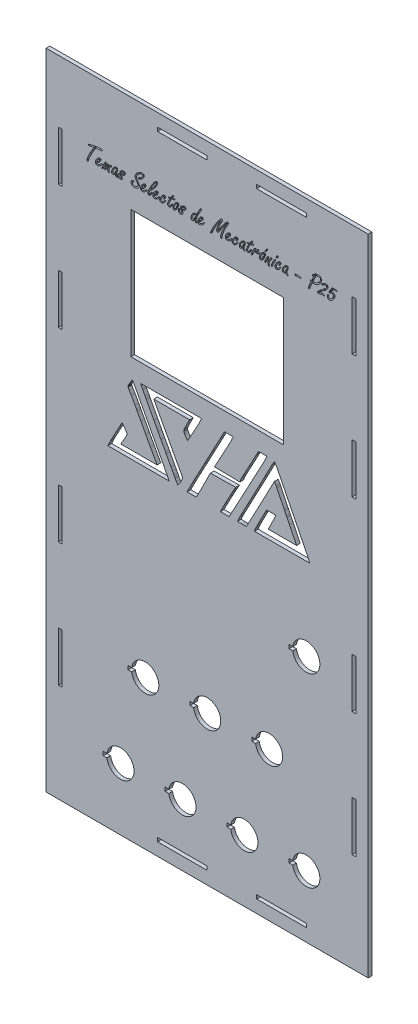
SolidWorks part; units mm, degrees
ref_plane "Alzado" through (0, 0, 0) normal (0, 0, 1) x (1, 0, 0)
ref_plane "Planta" through (0, 0, 0) normal (0, 1, 0) x (1, 0, 0)
ref_plane "Vista lateral" through (0, 0, 0) normal (1, 0, 0) x (0, 0, -1)
sketch "Croquis1" plane through (0, 0, 0) normal (0, 0, 1) x (1, 0, 0)
  line L1 (-130, 260) -> (130, 260)
  line L2 (-130, 260) -> (-130, -260)
  line L3 (-130, -260) -> (130, -260)
  line L4 (130, 260) -> (130, -260)
  line L5 (-130, 260) -> (130, -260) construction
  line L6 (-130, -260) -> (130, 260) construction
  point P0 (0, 0)
  dimension "D1" = 260
  dimension "D2" = 520
extrude "Saliente-Extruir1" add sketch "Croquis1" along normal blind 3
sketch "Croquis2" plane through (0, 0, 3) normal (0, 0, 1) x (1, 0, 0)
  line L4 (-117, -40.25) -> (-120, -40.25)
  line L5 (-117, -80.25) -> (-117, -40.25)
  line L6 (-120, -80.25) -> (-117, -80.25)
  line L7 (-120, -40.25) -> (-120, -80.25)
  line L8 (-117, -40.25) -> (-120, -40.25)
  line L9 (-117, -80.25) -> (-117, -40.25)
  line L10 (-120, -80.25) -> (-117, -80.25)
  line L11 (-120, -40.25) -> (-120, -80.25)
  line L12 (-117, 109.75) -> (-120, 109.75)
  line L13 (-117, 69.75) -> (-117, 109.75)
  line L14 (-120, 69.75) -> (-117, 69.75)
  line L15 (-120, 109.75) -> (-120, 69.75)
  line L16 (-117, 109.75) -> (-120, 109.75)
  line L17 (-117, 69.75) -> (-117, 109.75)
  line L18 (-120, 69.75) -> (-117, 69.75)
  line L19 (-120, 109.75) -> (-120, 69.75)
  line L20 (-117, 209.75) -> (-120, 209.75)
  line L21 (-117, 169.75) -> (-117, 209.75)
  line L22 (-120, 169.75) -> (-117, 169.75)
  line L23 (-120, 209.75) -> (-120, 169.75)
  line L24 (-117, 209.75) -> (-120, 209.75)
  line L25 (-117, 169.75) -> (-117, 209.75)
  line L26 (-120, 169.75) -> (-117, 169.75)
  line L27 (-120, 209.75) -> (-120, 169.75)
  line L28 (0, 249.75) -> (-40, 249.75)
  line L29 (0, 246.75) -> (0, 249.75)
  line L30 (-40, 246.75) -> (0, 246.75)
  line L31 (-40, 249.75) -> (-40, 246.75)
  line L32 (0, 249.75) -> (-40, 249.75)
  line L33 (0, 246.75) -> (0, 249.75)
  line L34 (-40, 246.75) -> (0, 246.75)
  line L35 (-40, 249.75) -> (-40, 246.75)
  line L36 (-117, -140.25) -> (-120, -140.25)
  line L37 (-117, -180.25) -> (-117, -140.25)
  line L38 (-120, -180.25) -> (-117, -180.25)
  line L39 (-120, -140.25) -> (-120, -180.25)
  line L40 (-117, -140.25) -> (-120, -140.25)
  line L41 (-117, -180.25) -> (-117, -140.25)
  line L42 (-120, -180.25) -> (-117, -180.25)
  line L43 (-120, -140.25) -> (-120, -180.25)
  line L44 (117, -140.25) -> (117, -180.25)
  line L45 (117, -180.25) -> (120, -180.25)
  line L46 (120, -180.25) -> (120, -140.25)
  line L47 (120, -140.25) -> (117, -140.25)
  line L48 (117, -140.25) -> (117, -180.25)
  line L49 (117, -180.25) -> (120, -180.25)
  line L50 (120, -180.25) -> (120, -140.25)
  line L51 (120, -140.25) -> (117, -140.25)
  line L52 (80, 249.75) -> (40, 249.75)
  line L53 (40, 249.75) -> (40, 246.75)
  line L54 (40, 246.75) -> (80, 246.75)
  line L55 (80, 246.75) -> (80, 249.75)
  line L56 (80, 249.75) -> (40, 249.75)
  line L57 (40, 249.75) -> (40, 246.75)
  line L58 (40, 246.75) -> (80, 246.75)
  line L59 (80, 246.75) -> (80, 249.75)
  line L60 (80, -249.75) -> (80, -246.75)
  line L61 (80, -246.75) -> (40, -246.75)
  line L62 (40, -246.75) -> (40, -249.75)
  line L63 (40, -249.75) -> (80, -249.75)
  line L64 (80, -249.75) -> (80, -246.75)
  line L65 (80, -246.75) -> (40, -246.75)
  line L66 (40, -246.75) -> (40, -249.75)
  line L67 (40, -249.75) -> (80, -249.75)
  line L68 (117, 209.75) -> (117, 169.75)
  line L69 (117, 169.75) -> (120, 169.75)
  line L70 (120, 169.75) -> (120, 209.75)
  line L71 (120, 209.75) -> (117, 209.75)
  line L72 (117, 209.75) -> (117, 169.75)
  line L73 (117, 169.75) -> (120, 169.75)
  line L74 (120, 169.75) -> (120, 209.75)
  line L75 (120, 209.75) -> (117, 209.75)
  line L76 (117, 109.75) -> (117, 69.75)
  line L77 (117, 69.75) -> (120, 69.75)
  line L78 (120, 69.75) -> (120, 109.75)
  line L79 (120, 109.75) -> (117, 109.75)
  line L80 (117, 109.75) -> (117, 69.75)
  line L81 (117, 69.75) -> (120, 69.75)
  line L82 (120, 69.75) -> (120, 109.75)
  line L83 (120, 109.75) -> (117, 109.75)
  line L84 (117, -40.25) -> (117, -80.25)
  line L85 (117, -80.25) -> (120, -80.25)
  line L86 (120, -80.25) -> (120, -40.25)
  line L87 (120, -40.25) -> (117, -40.25)
  line L88 (117, -40.25) -> (117, -80.25)
  line L89 (117, -80.25) -> (120, -80.25)
  line L90 (120, -80.25) -> (120, -40.25)
  line L91 (120, -40.25) -> (117, -40.25)
  line L92 (0, -249.75) -> (0, -246.75)
  line L93 (0, -246.75) -> (-40, -246.75)
  line L94 (-40, -246.75) -> (-40, -249.75)
  line L95 (-40, -249.75) -> (0, -249.75)
  line L96 (0, -249.75) -> (0, -246.75)
  line L97 (0, -246.75) -> (-40, -246.75)
  line L98 (-40, -246.75) -> (-40, -249.75)
  line L99 (-40, -249.75) -> (0, -249.75)
  dimension "D1" = 0
  dimension "D2" = 0
  dimension "D3" = 0
  dimension "D4" = 0
  dimension "D5" = 0
  dimension "D6" = 0
  dimension "D7" = 0
  dimension "D8" = 0
  dimension "D9" = 0
  dimension "D10" = 0
  dimension "D11" = 0
  dimension "D12" = 0
extrude "Cortar-Extruir1" cut sketch "Croquis2" against normal blind 10
sketch "Croquis3" plane through (0, 0, 3) normal (0, 0, 1) x (1, 0, 0)
  line L0 (130, -260) -> (130, 260) construction
  line L1 (-61.5, 181.5) -> (61.5, 181.5)
  line L2 (-61.5, 181.5) -> (-61.5, 78.5)
  line L3 (-61.5, 78.5) -> (61.5, 78.5)
  line L4 (61.5, 181.5) -> (61.5, 78.5)
  line L5 (-61.5, 181.5) -> (61.5, 78.5) construction
  line L6 (-61.5, 78.5) -> (61.5, 181.5) construction
  line L7 (-130, -260) -> (130, -260) construction
  line L8 (66.1028, -208.5) -> (69.1028, -208.5)
  line L9 (66.1028, -208.5) -> (66.1028, -211.5)
  line L10 (66.1028, -211.5) -> (69.1028, -211.5)
  line L11 (16.1028, -208.5) -> (19.1028, -208.5)
  line L12 (16.1028, -208.5) -> (16.1028, -211.5)
  line L13 (16.1028, -211.5) -> (19.1028, -211.5)
  line L14 (-33.8972, -208.5) -> (-30.8972, -208.5)
  line L15 (-33.8972, -208.5) -> (-33.8972, -211.5)
  line L16 (-33.8972, -211.5) -> (-30.8972, -211.5)
  line L23 (69.1028, -211.5) -> (19.1028, -211.5) construction
  line L24 (36.1028, -138.5) -> (39.1028, -138.5)
  line L25 (36.1028, -138.5) -> (36.1028, -141.5)
  line L26 (36.1028, -141.5) -> (39.1028, -141.5)
  line L27 (-13.8972, -138.5) -> (-10.8972, -138.5)
  line L28 (-13.8972, -141.5) -> (-10.8972, -141.5)
  line L29 (-13.8972, -138.5) -> (-13.8972, -141.5)
  line L33 (36.1028, -138.5) -> (-13.8972, -138.5) construction
  line L34 (-83.8972, -208.5) -> (-80.8972, -208.5)
  line L35 (0, -260) -> (0, -84.2648) construction
  line L36 (-83.8972, -208.5) -> (-80.8972, -208.5) [skipped]
  line L37 (-83.8972, -211.5) -> (-80.8972, -211.5) [skipped]
  line L38 (-83.8972, -208.5) -> (-83.8972, -211.5) [skipped]
  line L39 (-133.8972, -208.5) -> (-130.8972, -208.5) [skipped]
  line L40 (-133.8972, -211.5) -> (-130.8972, -211.5) [skipped]
  line L41 (-133.8972, -208.5) -> (-133.8972, -211.5) [skipped]
  line L42 (-83.8972, -211.5) -> (-80.8972, -211.5)
  line L43 (-63.8972, -138.5) -> (-60.8972, -138.5) [skipped]
  line L44 (-63.8972, -141.5) -> (-60.8972, -141.5) [skipped]
  line L45 (-63.8972, -138.5) -> (-63.8972, -141.5) [skipped]
  line L46 (-83.8972, -208.5) -> (-83.8972, -211.5)
  line L47 (-33.8972, -208.5) -> (-83.8972, -208.5) construction
  line L48 (-63.8972, -138.5) -> (-60.8972, -138.5)
  line L49 (-63.8972, -141.5) -> (-60.8972, -141.5)
  line L50 (-63.8972, -138.5) -> (-63.8972, -141.5)
  line L51 (-13.8972, -138.5) -> (-63.8972, -138.5) construction
  line L52 (66.1028, -58.75) -> (69.1028, -58.75)
  line L53 (66.1028, -58.75) -> (66.1028, -61.75)
  line L54 (66.1028, -61.75) -> (69.1028, -61.75)
  line L55 (117, -40.25) -> (117, -80.25) construction
  line L56 (-98.5917, 197.9337) -> (98.5917, 197.9337) construction
  line L57 (0, 181.5) -> (0, 197.9337) construction
  arc A0 (69.1028, -211.5) -> (69.1028, -208.5) centre (80, -210) ccw
  arc A2 (19.1028, -211.5) -> (19.1028, -208.5) centre (30, -210) ccw
  arc A3 (-30.8972, -211.5) -> (-30.8972, -208.5) centre (-20, -210) ccw
  arc A6 (39.1028, -141.5) -> (39.1028, -138.5) centre (50, -140) ccw
  arc A7 (-10.8972, -141.5) -> (-10.8972, -138.5) centre (0, -140) ccw
  arc A9 (-80.8972, -211.5) -> (-80.8972, -208.5) centre (-70, -210) ccw [skipped]
  arc A10 (-130.8972, -211.5) -> (-130.8972, -208.5) centre (-120, -210) ccw [skipped]
  arc A11 (-60.8972, -141.5) -> (-60.8972, -138.5) centre (-50, -140) ccw [skipped]
  arc A12 (-80.8972, -211.5) -> (-80.8972, -208.5) centre (-70, -210) ccw
  arc A13 (-60.8972, -141.5) -> (-60.8972, -138.5) centre (-50, -140) ccw
  arc A14 (69.1028, -61.75) -> (69.1028, -58.75) centre (80, -60.25) ccw
  text T0 "Temas Selectos de Mecatrónica - P25" font "Freestyle Script" height 13
  point P0 (0, 130)
  point P87 (-98.5917, 197.9337)
  point P90 (117, -60.25)
  dimension "D4" = 22
  dimension "D12" = 11
  dimension "D23" = 11
  dimension "D1" = 123
  dimension "D2" = 103
  dimension "D3" = 130
  dimension "D5" = 50
  dimension "D6" = 50
  dimension "D7" = 3
  dimension "D8" = 3
  dimension "D9" = 3
  dimension "D11" = 50
  dimension "D13" = 3
  dimension "D14" = 3
  dimension "D15" = 3
  dimension "D16" = 120
  dimension "D18" = 50
  dimension "D20" = 50
  dimension "D22" = 50
  dimension "D24" = 3
  dimension "D25" = 3
  dimension "D26" = 3
  dimension "D27" = 50
  dimension "D28" = 0
  dimension "D10" = 5
  dimension "D17" = 3
  dimension "D19" = 2
  dimension "D21" = 2
extrude "Cortar-Extruir2" cut sketch "Croquis3" against normal blind 3
sketch "Croquis6" plane through (0, 0, 3) normal (0, 0, 1) x (1, 0, 0)
  line L228 (54.3433, 63.1689) -> (55.5235, 61.4472)
  line L229 (55.5235, 61.4472) -> (56.5036, 59.6034)
  line L230 (56.5036, 59.6034) -> (56.8423, 58.9285)
  line L231 (56.8423, 58.9285) -> (57.959, 56.6912)
  line L232 (57.959, 56.6912) -> (58.7623, 55.0866)
  line L233 (58.7623, 55.0866) -> (60.9386, 50.7297)
  line L234 (60.9386, 50.7297) -> (63.2158, 46.1729)
  line L235 (63.2158, 46.1729) -> (67.0376, 38.5215)
  line L236 (67.0376, 38.5215) -> (71.46, 29.67)
  line L237 (71.46, 29.67) -> (75.7126, 21.1604)
  line L238 (75.7126, 21.1604) -> (77.5237, 17.5362)
  line L239 (77.5237, 17.5362) -> (79.6535, 13.2709)
  line L240 (79.6535, 13.2709) -> (80.4366, 11.7035)
  line L241 (80.4366, 11.7035) -> (81.5021, 9.5683)
  line L242 (81.5021, 9.5683) -> (81.818, 8.9381)
  line L243 (81.818, 8.9381) -> (82.9051, 6.3814)
  line L244 (82.9051, 6.3814) -> (38.2144, 6.3814)
  line L245 (38.2144, 6.3814) -> (38.7888, 8.1493)
  line L246 (38.7888, 8.1493) -> (39.5676, 9.8375)
  line L247 (39.5676, 9.8375) -> (39.8779, 10.4579)
  line L248 (39.8779, 10.4579) -> (40.8815, 12.4508)
  line L249 (40.8815, 12.4508) -> (41.5703, 13.8218)
  line L250 (41.5703, 13.8218) -> (46.608, 23.5355)
  line L251 (46.608, 23.5355) -> (47.9589, 26.2066)
  line L252 (47.9589, 26.2066) -> (55.3514, 26.2066)
  line L253 (55.3514, 26.2066) -> (54.4794, 23.8834)
  line L254 (54.4794, 23.8834) -> (53.4377, 21.6415)
  line L255 (53.4377, 21.6415) -> (53.1194, 21.0071)
  line L256 (53.1194, 21.0071) -> (51.9492, 18.6882)
  line L257 (51.9492, 18.6882) -> (49.303, 13.4379)
  line L258 (49.303, 13.4379) -> (72.1524, 13.4379)
  line L259 (72.1524, 13.4379) -> (66.4621, 25.1611)
  line L260 (66.4621, 25.1611) -> (64.4279, 29.2111)
  line L261 (64.4279, 29.2111) -> (63.9894, 30.0855)
  line L262 (63.9894, 30.0855) -> (62.6388, 32.78)
  line L263 (62.6388, 32.78) -> (62.1699, 33.7159)
  line L264 (62.1699, 33.7159) -> (56.3958, 45.5332)
  line L265 (56.3958, 45.5332) -> (56.0103, 46.3534)
  line L266 (56.0103, 46.3534) -> (55.6932, 47.0357)
  line L267 (55.6932, 47.0357) -> (54.3433, 49.3921)
  line L268 (54.3433, 49.3921) -> (53.8829, 48.4915)
  line L269 (53.8829, 48.4915) -> (46.0738, 33.6153)
  line L270 (46.0738, 33.6153) -> (42.2466, 26.3747)
  line L271 (42.2466, 26.3747) -> (37.3483, 17.1719)
  line L272 (37.3483, 17.1719) -> (33.0879, 9.1185)
  line L273 (33.0879, 9.1185) -> (32.6031, 8.181)
  line L274 (32.6031, 8.181) -> (32.1743, 7.3477)
  line L275 (32.1743, 7.3477) -> (31.4939, 6.3814)
  line L276 (31.4939, 6.3814) -> (29.9175, 6.3486)
  line L277 (29.9175, 6.3486) -> (28.9561, 6.3519)
  line L278 (28.9561, 6.3519) -> (27.9447, 6.3604)
  line L279 (27.9447, 6.3604) -> (26.9295, 6.365)
  line L280 (26.9295, 6.365) -> (24.4375, 6.3814)
  line L281 (24.4375, 6.3814) -> (26.136, 10.0974)
  line L282 (26.136, 10.0974) -> (26.4387, 10.6842)
  line L283 (26.4387, 10.6842) -> (27.4197, 12.5768)
  line L284 (27.4197, 12.5768) -> (27.762, 13.2376)
  line L285 (27.762, 13.2376) -> (32.6259, 22.3318)
  line L286 (32.6259, 22.3318) -> (37.2207, 31.0901)
  line L287 (37.2207, 31.0901) -> (41.5326, 39.2274)
  line L288 (41.5326, 39.2274) -> (46.6149, 48.888)
  line L289 (46.6149, 48.888) -> (52.0087, 59.3309)
  line L290 (52.0087, 59.3309) -> (54.3433, 63.1689)
  line L291 (14.0208, 63.8408) -> (21.0773, 63.8408)
  line L292 (21.0773, 63.8408) -> (19.1583, 59.7574)
  line L293 (19.1583, 59.7574) -> (18.7875, 59.057)
  line L294 (18.7875, 59.057) -> (17.5911, 56.8054)
  line L295 (17.5911, 56.8054) -> (16.7613, 55.2423)
  line L296 (16.7613, 55.2423) -> (10.3246, 43.3436)
  line L297 (10.3246, 43.3436) -> (5.9563, 35.2791)
  line L298 (5.9563, 35.2791) -> (26.4536, 34.9431)
  line L299 (26.4536, 34.9431) -> (27.1256, 36.9592)
  line L300 (27.1256, 36.9592) -> (27.9316, 38.5868)
  line L301 (27.9316, 38.5868) -> (28.4129, 39.5075)
  line L302 (28.4129, 39.5075) -> (28.9317, 40.4874)
  line L303 (28.9317, 40.4874) -> (29.4775, 41.5258)
  line L304 (29.4775, 41.5258) -> (33.5517, 49.0734)
  line L305 (33.5517, 49.0734) -> (39.0172, 59.2966)
  line L306 (39.0172, 59.2966) -> (39.729, 60.6421)
  line L307 (39.729, 60.6421) -> (40.0584, 61.2679)
  line L308 (40.0584, 61.2679) -> (41.5745, 63.8408)
  line L309 (41.5745, 63.8408) -> (43.1102, 63.9393)
  line L310 (43.1102, 63.9393) -> (44.0225, 63.9294)
  line L311 (44.0225, 63.9294) -> (44.9767, 63.9039)
  line L312 (44.9767, 63.9039) -> (45.9388, 63.8901)
  line L313 (45.9388, 63.8901) -> (48.2949, 63.8408)
  line L314 (48.2949, 63.8408) -> (46.817, 60.566)
  line L315 (46.817, 60.566) -> (46.3356, 59.642)
  line L316 (46.3356, 59.642) -> (45.8168, 58.6535)
  line L317 (45.8168, 58.6535) -> (45.271, 57.6106)
  line L318 (45.271, 57.6106) -> (41.1894, 50.0326)
  line L319 (41.1894, 50.0326) -> (36.7022, 41.6635)
  line L320 (36.7022, 41.6635) -> (31.3587, 31.7325)
  line L321 (31.3587, 31.7325) -> (26.9576, 23.5184)
  line L322 (26.9576, 23.5184) -> (20.4843, 11.5088)
  line L323 (20.4843, 11.5088) -> (17.7171, 6.3814)
  line L324 (17.7171, 6.3814) -> (10.6606, 6.3814)
  line L325 (10.6606, 6.3814) -> (14.2828, 13.4762)
  line L326 (14.2828, 13.4762) -> (18.0531, 20.4942)
  line L327 (18.0531, 20.4942) -> (18.6436, 21.5828)
  line L328 (18.6436, 21.5828) -> (20.3002, 24.6315)
  line L329 (20.3002, 24.6315) -> (20.802, 25.5544)
  line L330 (20.802, 25.5544) -> (21.2702, 26.4126)
  line L331 (21.2702, 26.4126) -> (21.6754, 27.156)
  line L332 (21.6754, 27.156) -> (23.0934, 29.5668)
  line L333 (23.0934, 29.5668) -> (2.5961, 29.2307)
  line L334 (2.5961, 29.2307) -> (0.5236, 25.0738)
  line L335 (0.5236, 25.0738) -> (-0.7857, 22.4506)
  line L336 (-0.7857, 22.4506) -> (-2.8584, 18.2964)
  line L337 (-2.8584, 18.2964) -> (-4.5316, 14.9433)
  line L338 (-4.5316, 14.9433) -> (-5.1662, 13.6706)
  line L339 (-5.1662, 13.6706) -> (-6.0632, 11.8739)
  line L340 (-6.0632, 11.8739) -> (-6.5765, 10.8451)
  line L341 (-6.5765, 10.8451) -> (-8.8286, 6.7174)
  line L342 (-8.8286, 6.7174) -> (-16.221, 6.7174)
  line L343 (-16.221, 6.7174) -> (-11.7622, 15.4982)
  line L344 (-11.7622, 15.4982) -> (-7.1188, 24.1829)
  line L345 (-7.1188, 24.1829) -> (-2.5492, 32.717)
  line L346 (-2.5492, 32.717) -> (-2.1602, 33.4529)
  line L347 (-2.1602, 33.4529) -> (-0.5903, 36.4247)
  line L348 (-0.5903, 36.4247) -> (3.4992, 44.1417)
  line L349 (3.4992, 44.1417) -> (3.8542, 44.81)
  line L350 (3.8542, 44.81) -> (10.8027, 57.8117)
  line L351 (10.8027, 57.8117) -> (14.0208, 63.8408)
  line L352 (-53.519, 63.8408) -> (-4.4601, 63.8408)
  line L353 (-4.4601, 63.8408) -> (-6.1822, 60.1512)
  line L354 (-6.1822, 60.1512) -> (-6.8129, 58.9745)
  line L355 (-6.8129, 58.9745) -> (-7.4842, 57.7295)
  line L356 (-7.4842, 57.7295) -> (-8.1714, 56.4517)
  line L357 (-8.1714, 56.4517) -> (-11.9579, 49.5222)
  line L358 (-11.9579, 49.5222) -> (-15.8847, 42.6716)
  line L359 (-15.8847, 42.6716) -> (-17.9849, 45.8428)
  line L360 (-17.9849, 45.8428) -> (-18.5362, 46.7865)
  line L361 (-18.5362, 46.7865) -> (-18.8203, 47.8062)
  line L362 (-18.8203, 47.8062) -> (-18.5729, 49.392)
  line L363 (-18.5729, 49.392) -> (-14.2046, 58.1285)
  line L364 (-14.2046, 58.1285) -> (-43.1024, 58.1285)
  line L365 (-43.1024, 58.1285) -> (-36.067, 45.0657)
  line L366 (-36.067, 45.0657) -> (-31.1947, 35.9932)
  line L367 (-31.1947, 35.9932) -> (-30.5637, 34.8153)
  line L368 (-30.5637, 34.8153) -> (-27.6725, 29.4108)
  line L369 (-27.6725, 29.4108) -> (-26.6931, 27.5789)
  line L370 (-26.6931, 27.5789) -> (-25.4207, 25.1939)
  line L371 (-25.4207, 25.1939) -> (-22.4634, 19.8248)
  line L372 (-22.4634, 19.8248) -> (-21.9315, 18.8922)
  line L373 (-21.9315, 18.8922) -> (-20.9451, 17.2055)
  line L374 (-20.9451, 17.2055) -> (-20.196, 15.7219)
  line L375 (-20.196, 15.7219) -> (-19.8842, 14.1046)
  line L376 (-19.8842, 14.1046) -> (-20.8061, 12.1373)
  line L377 (-20.8061, 12.1373) -> (-21.9541, 10.2876)
  line L378 (-21.9541, 10.2876) -> (-22.4352, 9.5381)
  line L379 (-22.4352, 9.5381) -> (-23.6132, 7.7254)
  line L380 (-23.6132, 7.7254) -> (-24.787, 9.4191)
  line L381 (-24.787, 9.4191) -> (-25.7921, 11.2222)
  line L382 (-25.7921, 11.2222) -> (-26.1306, 11.8624)
  line L383 (-26.1306, 11.8624) -> (-26.8507, 13.2289)
  line L384 (-26.8507, 13.2289) -> (-27.992, 15.3922)
  line L385 (-27.992, 15.3922) -> (-29.1698, 17.6205)
  line L386 (-29.1698, 17.6205) -> (-33.0218, 24.8625)
  line L387 (-33.0218, 24.8625) -> (-33.6535, 26.0435)
  line L388 (-33.6535, 26.0435) -> (-37.3929, 32.8015)
  line L389 (-37.3929, 32.8015) -> (-39.6792, 37.1692)
  line L390 (-39.6792, 37.1692) -> (-42.8924, 43.3016)
  line L391 (-42.8924, 43.3016) -> (-49.0141, 54.7294)
  line L392 (-49.0141, 54.7294) -> (-49.3882, 55.4381)
  line L393 (-49.3882, 55.4381) -> (-50.1161, 56.8187)
  line L394 (-50.1161, 56.8187) -> (-51.8722, 60.0933)
  line L395 (-51.8722, 60.0933) -> (-52.2066, 60.7055)
  line L396 (-52.2066, 60.7055) -> (-53.1071, 62.3418)
  line L397 (-53.1071, 62.3418) -> (-53.4675, 63.1494)
  line L398 (-53.4675, 63.1494) -> (-53.519, 63.8408)
  line L399 (-60.5754, 62.8328) -> (-59.3016, 61.3348)
  line L400 (-59.3016, 61.3348) -> (-58.3466, 59.6052)
  line L401 (-58.3466, 59.6052) -> (-57.9915, 58.9302)
  line L402 (-57.9915, 58.9302) -> (-56.8372, 56.7215)
  line L403 (-56.8372, 56.7215) -> (-56.0214, 55.168)
  line L404 (-56.0214, 55.168) -> (-54.3403, 51.9642)
  line L405 (-54.3403, 51.9642) -> (-51.0112, 45.6782)
  line L406 (-51.0112, 45.6782) -> (-49.2518, 42.3697)
  line L407 (-49.2518, 42.3697) -> (-48.8966, 41.7014)
  line L408 (-48.8966, 41.7014) -> (-46.246, 36.6941)
  line L409 (-46.246, 36.6941) -> (-44.6774, 33.7251)
  line L410 (-44.6774, 33.7251) -> (-44.2891, 32.9901)
  line L411 (-44.2891, 32.9901) -> (-39.6581, 24.3795)
  line L412 (-39.6581, 24.3795) -> (-35.2689, 16.126)
  line L413 (-35.2689, 16.126) -> (-34.6956, 15.0202)
  line L414 (-34.6956, 15.0202) -> (-30.6696, 7.0535)
  line L415 (-30.6696, 7.0535) -> (-80.0646, 7.0535)
  line L416 (-80.0646, 7.0535) -> (-78.4396, 10.6224)
  line L417 (-78.4396, 10.6224) -> (-77.8654, 11.7322)
  line L418 (-77.8654, 11.7322) -> (-77.2504, 12.9128)
  line L419 (-77.2504, 12.9128) -> (-76.9356, 13.5187)
  line L420 (-76.9356, 13.5187) -> (-71.1246, 24.3467)
  line L421 (-71.1246, 24.3467) -> (-68.6399, 28.8948)
  line L422 (-68.6399, 28.8948) -> (-67.2132, 27.2407)
  line L423 (-67.2132, 27.2407) -> (-66.0147, 25.4086)
  line L424 (-66.0147, 25.4086) -> (-65.5744, 24.7365)
  line L425 (-65.5744, 24.7365) -> (-65.1681, 24.0776)
  line L426 (-65.1681, 24.0776) -> (-64.793, 23.4838)
  line L427 (-64.793, 23.4838) -> (-64.7148, 22.7161)
  line L428 (-64.7148, 22.7161) -> (-65.2797, 21.1663)
  line L429 (-65.2797, 21.1663) -> (-69.648, 13.4378)
  line L430 (-69.648, 13.4378) -> (-40.4142, 13.4378)
  line L431 (-40.4142, 13.4378) -> (-45.7905, 23.1824)
  line L432 (-45.7905, 23.1824) -> (-49.6259, 30.3373)
  line L433 (-49.6259, 30.3373) -> (-53.571, 37.6505)
  line L434 (-53.571, 37.6505) -> (-56.3752, 42.8514)
  line L435 (-56.3752, 42.8514) -> (-56.9743, 43.97)
  line L436 (-56.9743, 43.97) -> (-58.1577, 46.1845)
  line L437 (-58.1577, 46.1845) -> (-61.1201, 51.4528)
  line L438 (-61.1201, 51.4528) -> (-61.6996, 52.4304)
  line L439 (-61.6996, 52.4304) -> (-62.8003, 54.2364)
  line L440 (-62.8003, 54.2364) -> (-63.8055, 56.0999)
  line L441 (-63.8055, 56.0999) -> (-63.8794, 56.6484)
  line L442 (-63.8794, 56.6484) -> (-63.7912, 57.3279)
  line L443 (-63.7912, 57.3279) -> (-63.2636, 58.1286)
  line L444 (-63.2636, 58.1286) -> (-62.6099, 59.3217)
  line L445 (-62.6099, 59.3217) -> (-61.8775, 60.5857)
  line L446 (-61.8775, 60.5857) -> (-61.4982, 61.2427)
  line L447 (-61.4982, 61.2427) -> (-60.5754, 62.8328)
extrude "Cortar-Extruir3" cut sketch "Croquis6" against normal blind 3
